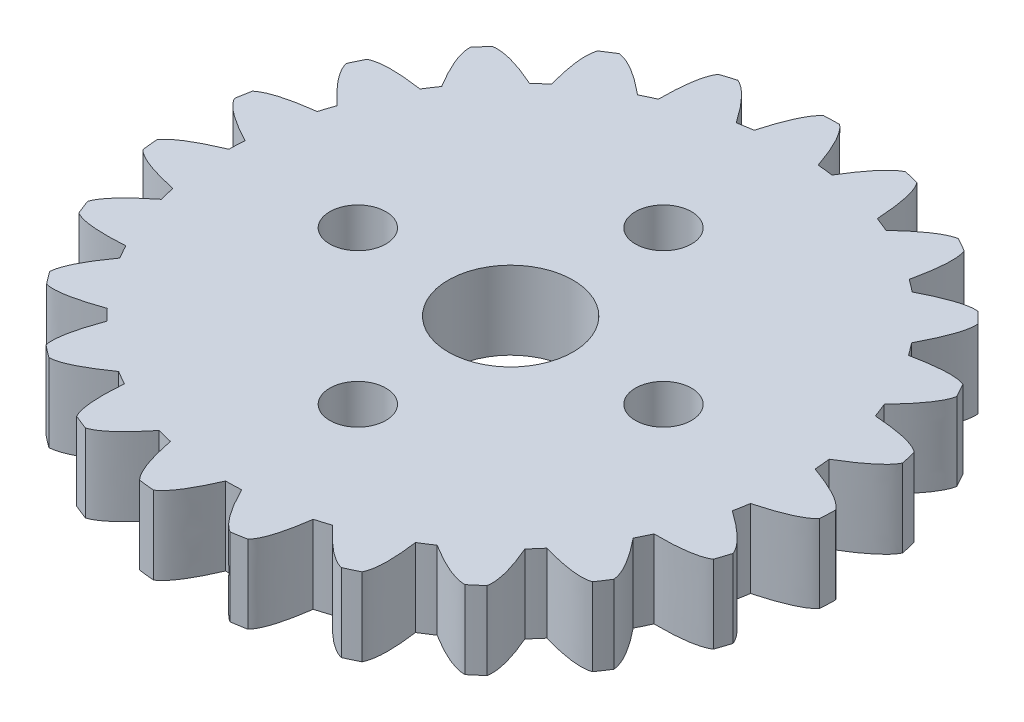
SolidWorks part; units mm, degrees
material "ABS"
ref_plane "Front Plane" through (0, 0, 0) normal (0, 0, 1) x (1, 0, 0)
ref_plane "Top Plane" through (0, 0, 0) normal (0, 1, 0) x (1, 0, 0)
ref_plane "Right Plane" through (0, 0, 0) normal (1, 0, 0) x (0, 0, -1)
sketch "Sketch1" plane through (0, 0, 0) normal (0, 1, 0) x (1, 0, 0)
  line L0 (11.5353, 14.2102) -> (14.3418, 11.3712) construction
  line L2 (12.9386, 12.7907) -> (15.072, 14.8998) construction
  line L3 (15.072, 14.8998) -> (15.2104, 15.0366)
  circle A0 centre (0, 0) radius 18.3028
  circle A1 centre (0, 0) radius 21.1937
  spline S0 degree 2 poles (14.3418, 11.3712) (17.4822, 17.2825) (11.5353, 14.2102) knots 0 0 0 1 1 1
  point P3 (11.5353, 14.2102)
  point P4 (14.3418, 11.3712)
  point P6 (14.7163, 15.2512)
  point P12 (10.7421, 14.8189)
  point P14 (15.2104, 15.0366)
  point P15 (15.4194, 14.5401)
  point P16 (7.7366, 16.5873)
  dimension "D1" = 36.6056
  dimension "D4" = 3
  dimension "D5" = 1
  dimension "D2" = 4
  dimension "D3" = 1
extrude "Boss-Extrude4" add sketch "Sketch1" along normal blind 5 contours A0 | A0 S0 A1 region at (13.8583, 0, -13.7) region at (0, 0, 0)
pattern_circular "CirPattern6" count 23 every 15.652 about axis through (0, 5, 0) along (0, 1, 0) of "Boss-Extrude4"
sketch "Sketch2" plane through (0, 5, 0) normal (0, 1, 0) x (1, 0, 0)
  circle A0 centre (0, 0) radius 4
  circle A1 centre (9.8, 0) radius 1.8
  dimension "D1" = 8
  dimension "D2" = 3.6
extrude "Cut-Extrude1" cut sketch "Sketch2" against normal blind 10 contours A0 region at (0, 5, 0)
sketch "Sketch5" plane through (0, 5, 0) normal (0, 1, 0) x (1, 0, 0)
  circle A1 centre (9.8, 0) radius 1.8
  dimension "D1" = 3.6
extrude "Cut-Extrude2" cut sketch "Sketch5" against normal blind 10
pattern_circular "CirPattern7" count 4 over 360 about axis through (0, 5, 0) along (0, 1, 0) of "Cut-Extrude2"
equation "\"number-of-teeth\"= 23"
equation "\"gear-size\"= 4mm"
equation "\"circumference\"= \"number-of-teeth\" * ( ( 1 + \"space-between-teeth\" ) * \"gear-size\" )"
equation "\"space-between-teeth\"= .25"
equation "\"D1@Sketch1\" = \"circumference\" / pi"
equation "\"D2@Sketch1\"=\"gear-size\""
equation "\"gear-length\"= 3mm"
equation "\"D4@Sketch1\"=\"gear-length\""
equation "\"D5@Sketch1\"=\"gear-size\" * \"space-between-teeth\""
equation "\"D3@Sketch1\"=\"gear-size\" * \"space-between-teeth\""
equation "\"D1@CirPattern6\"=\"number-of-teeth\""
equation "\"D2@CirPattern6\"=360 / \"number-of-teeth\""
